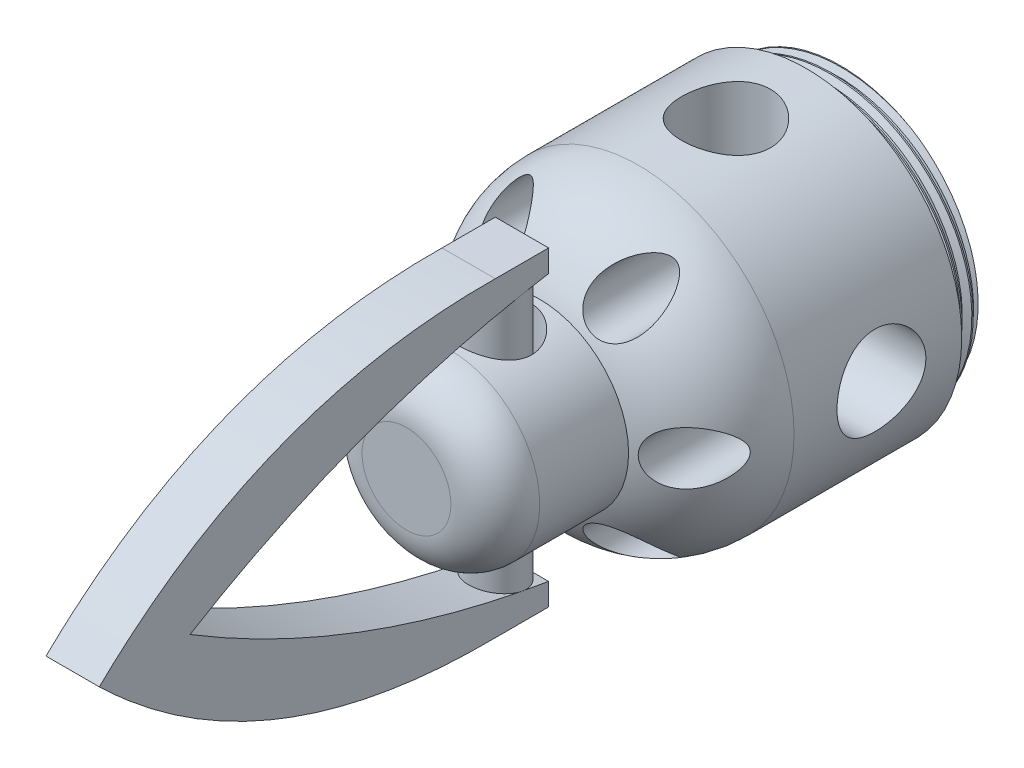
SolidWorks part; units mm, degrees
ref_plane "Plan de face" through (0, 0, 0) normal (0, 0, 1) x (1, 0, 0)
ref_plane "Plan de dessus" through (0, 0, 0) normal (0, 1, 0) x (1, 0, 0)
ref_plane "Plan de droite" through (0, 0, 0) normal (1, 0, 0) x (0, 0, -1)
sketch "Esquisse1" plane through (0, 0, 0) normal (0, 0, 1) x (1, 0, 0)
  circle A0 centre (0, 0) radius 15.85
extrude "Boss.-Extru.1" add sketch "Esquisse1" along normal blind 5.6
thread "Filetage1" pitch 1.27 method cut profile "Profil de filetage2" start angle 0, offset 1, length 0, pitch 1.27, diameter 31.7
ref_plane "Plan2" through (15.85, 0, -1) normal (0, -1, 0) x (1, 0, 0)
sketch "Profil de filetage2" plane through (15.85, 0, -1) normal (0, -1, 0) x (1, 0, 0)
  line L0 (0, 0) -> (0, 1.27) construction
  line L11 (0, 0) -> (0, 1.1112)
  line L12 (0, 1.1112) -> (-0.6874, 0.7144)
  line L13 (-0.6874, 0.7144) -> (-0.6874, 0.3969)
  line L15 (-0.6874, 0.3969) -> (0, 0)
  line L17 (-0.6874, 0.5556) -> (0, 0.5556) construction
  point P2 (0, 0)
  dimension "Pitch" = 1.27
  dimension "Profile_Angle" = 60
  dimension "Profile_Land" = 0.3175
  dimension "Profile_Height" = 0.6874
sketch "Esquisse23" plane through (0, 0, 0) normal (0, 0, -1) x (-1, 0, 0)
  circle A0 centre (0, 0) radius 12.75
extrude "Enlèv. mat.-Extru.1" cut sketch "Esquisse23" against normal blind 10
sketch "Esquisse24" plane through (0, 0, 5.6) normal (0, 0, 1) x (1, 0, 0)
  circle A0 centre (0, 0) radius 17.5
extrude "Boss.-Extru.3" add sketch "Esquisse24" along normal blind 30 separate body
sketch "Esquisse25" plane through (0, 0, 35.6) normal (0, 0, 1) x (1, 0, 0)
  circle A0 centre (0, 0) radius 10
extrude "Boss.-Extru.4" add sketch "Esquisse25" along normal blind 15
fillet "Congé1" radius 5 1 edges at (10, 0, 50.6)
fillet "Congé2" radius 12 1 edges at (17.5, 0, 35.6)
sketch "Esquisse29" plane through (0, 0, 5.6) normal (0, 0, -1) x (-1, 0, 0)
  circle A0 centre (0, 0) radius 9.9333
extrude "Enlèv. mat.-Extru.3" cut sketch "Esquisse29" against normal blind 10.485
sketch "Esquisse31" plane through (0, 0, 0) normal (0, 0, -1) x (-1, 0, 0)
  line L1 (-28.3572, -19.5675) -> (28.3572, -19.5675)
  line L2 (-28.3572, -19.5675) -> (-28.3572, 19.5675)
  line L3 (-28.3572, 19.5675) -> (28.3572, 19.5675)
  line L4 (28.3572, -19.5675) -> (28.3572, 19.5675)
  line L5 (-28.3572, -19.5675) -> (28.3572, 19.5675) construction
  line L6 (-28.3572, 19.5675) -> (28.3572, -19.5675) construction
  point P0 (0, 0)
extrude "Enlèv. mat.-Extru.4" cut sketch "Esquisse31" against normal blind 1.75
sketch "Esquisse32" plane through (0, 0, 0) normal (0, 1, 0) x (1, 0, 0)
  circle A0 centre (0, -40.6) radius 4.0936
extrude "Enlèv. mat.-Extru.5" cut sketch "Esquisse32" against normal through all and the other way through all contours A0
sketch "Esquisse34" plane through (0, 0, 0) normal (0, 1, 0) x (1, 0, 0)
  circle A0 centre (0, -40.6) radius 3
extrude "Boss.-Extru.5" add sketch "Esquisse34" along normal blind 17.5 and the other way blind 17.5 separate body
sketch "Esquisse35" plane through (0, 0, 0) normal (1, 0, 0) x (0, 0, -1)
  line L0 (-43.6, 17.5) -> (-37.6, 17.5)
  line L1 (-37.6, 17.5) -> (-37.6, 15)
  line L2 (19.25, 0) -> (-19.25, 0) construction
  line L3 (-43.6, -17.5) -> (-37.6, -17.5)
  line L4 (-37.6, -15) -> (-37.6, -17.5)
  spline S0 degree 2 poles (-43.6, 17.5) (-69.7627, 17.8143) (-88.1715, 0) knots 0 0 0 1 1 1
  spline S1 degree 2 poles (-37.6, 15) (-59.1695, 11.4249) (-77.9633, 0) knots 0 0 0 1 1 1
  spline S2 degree 2 poles (-37.6, -15) (-59.1695, -11.4249) (-77.9633, 0) knots 0 0 0 1 1 1
  spline S3 degree 2 poles (-43.6, -17.5) (-69.7627, -17.8143) (-88.1715, 0) knots 0 0 0 1 1 1
  point P16 (0, 0)
  dimension "D1" = 2.5
extrude "Boss.-Extru.6" add sketch "Esquisse35" along normal blind 3 and the other way blind 3 contours S2 S1 L1 L0 S0 S3 L3 L4
ref_plane "Plan3" through (0, 0, 24.5) normal (0, 0, 1) x (1, 0, 0)
sketch "Esquisse37" plane through (0, 0, 24.5) normal (0, 0, 1) x (1, 0, 0)
  circle A2 centre (-13.75, 0) radius 3
  circle A3 centre (-6.875, 11.9078) radius 3
  circle A4 centre (6.875, 11.9078) radius 3
  circle A5 centre (13.75, 0) radius 3
  circle A6 centre (6.875, -11.9078) radius 3
  circle A7 centre (-6.875, -11.9078) radius 3
  point P16 (0, 0)
  dimension "D1" = 6
extrude "Enlèv. mat.-Extru.6" cut sketch "Esquisse37" along normal blind 14
sketch "Esquisse38" plane through (0, 0, 0) normal (0, 1, 0) x (1, 0, 0)
  circle A0 centre (0, -14.6391) radius 5
extrude "Enlèv. mat.-Extru.7" cut sketch "Esquisse38" against normal through all and the other way through all
pattern_circular "Répétition circulaire1" count 4 over 360 about axis through (0, 0, 35.6) along (0, 0, -1) of "Enlèv. mat.-Extru.7" reverse direction yes
